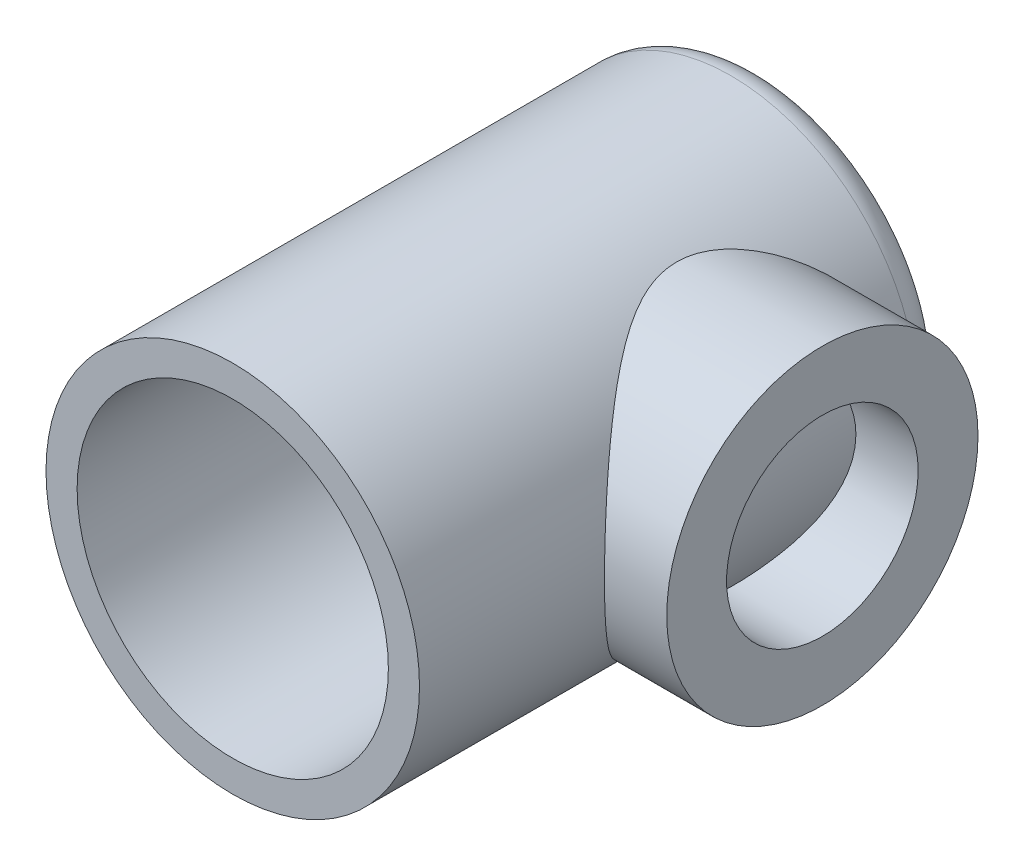
SolidWorks part; units mm, degrees
ref_plane "Front Plane" through (0, 0, 0) normal (0, 0, 1) x (1, 0, 0)
ref_plane "Top Plane" through (0, 0, 0) normal (0, 1, 0) x (1, 0, 0)
ref_plane "Right Plane" through (0, 0, 0) normal (1, 0, 0) x (0, 0, -1)
sketch "Sketch1" plane through (0, 0, 0) normal (0, 1, 0) x (1, 0, 0)
  line L0 (0, 0) -> (0, -8)
  line L1 (0, -2.501) -> (4, -2.501)
ref_plane "Plane1" through (0, 0, 8) normal (0, 0, 1) x (1, 0, 0)
sketch "Sketch2" plane through (0, 0, 8) normal (0, 0, 1) x (1, 0, 0)
  circle A0 centre (0, 0) radius 3
  circle A1 centre (0, 0) radius 2.5
extrude "Boss-Extrude1" add sketch "Sketch2" against normal up to vertex (8 mm away) up to point (0, 0, 0)
ref_plane "Plane2" through (4, 0, 2.501) normal (1, 0, 0) x (0, 0, -1)
sketch "Sketch3" plane through (4, 0, 2.501) normal (1, 0, 0) x (0, 0, -1)
  line L0 (2.501, 0) -> (-5.499, 0) construction
  circle A0 centre (-0.0128, 0) radius 2
  circle A1 centre (-0.0128, 0) radius 1.5
sketch "Sketch7" plane through (4, 0, 2.501) normal (1, 0, 0) x (0, 0, -1)
  line L0 (2.501, 0) -> (-5.499, 0) construction
  circle A0 centre (-0.027, 0) radius 2.5
  circle A1 centre (-0.027, 0) radius 1.5391
extrude "Boss-Extrude6" add sketch "Sketch7" against normal up to surface (1 mm away) up to face at (3, 0, 0)
sketch "Sketch8" plane through (0, 0, 0) normal (0, 0, -1) x (-1, 0, 0)
  circle A0 centre (0, 0) radius 3
extrude "Boss-Extrude7" add sketch "Sketch8" along normal blind 0.5
fillet "Fillet2" radius 0.5 1 edges at (-3, 0, -0.5)
